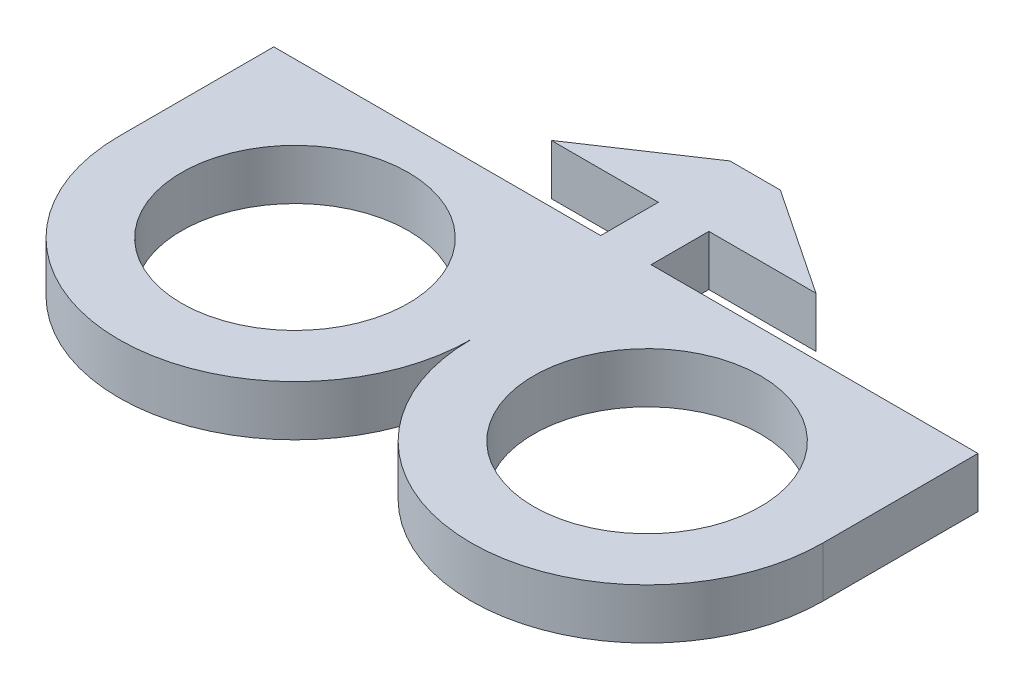
SolidWorks part; units mm, degrees
ref_plane "Front" through (0, 0, 0) normal (0, 0, 1) x (1, 0, 0)
ref_plane "Top" through (0, 0, 0) normal (0, 1, 0) x (1, 0, 0)
ref_plane "Right" through (0, 0, 0) normal (1, 0, 0) x (0, 0, -1)
sketch "Sketch1" plane through (0, 0, 0) normal (0, 1, 0) x (1, 0, 0)
  line L0 (-1.7907, 2.05) -> (-9.398, 2.05)
  line L2 (-1.7907, -2.05) -> (-1.7907, 2.05)
  line L4 (1.7907, -2.05) -> (1.7907, 2.05)
  line L7 (-9.398, 2.05) -> (-1.7907, 7.13)
  line L8 (-1.7907, 7.13) -> (1.7907, 7.13)
  line L9 (1.7907, 7.13) -> (9.398, 2.05)
  line L10 (9.398, 2.05) -> (1.7907, 2.05)
  line L11 (1.7907, -2.05) -> (25.0063, -2.05)
  line L12 (-1.7907, -2.05) -> (-25.0063, -2.05)
  line L13 (-25.0063, -2.05) -> (-25.0063, -13.0482)
  line L14 (-25.0063, -13.0482) -> (25.0063, -13.0482)
  line L15 (25.0063, -13.0482) -> (25.0063, -2.05)
  line L16 (25.0063, -2.05) -> (1.7907, -2.05)
  point P0 (0, 0)
  point P17 (0, 7.13)
  point P19 (0, -13.0482)
  point P24 (1.7907, 0)
  dimension "D1" = 18.796
  dimension "D2" = 3.5814
  dimension "D3" = 50.0126
  dimension "D4" = 10.9982
  dimension "D5" = 5.08
  dimension "D7" = 4.1
extrude "Boss-Extrude1" add sketch "Sketch1" along normal blind 3.5814 contours L14 L15 L11 L4 L10 L9 L8 L7 L0 L2 L12 L13 region at (0, 0, 6.3134)
sketch "Sketch3" plane through (0, 3.5814, 0) normal (0, 1, 0) x (1, 0, 0)
  line L3 (-25.0063, -13.0482) -> (25.0063, -13.0482) construction
  line L16 (-25.0063, -13.0482) -> (25.0063, -13.0482)
  line L17 (25.0063, -13.0482) -> (25.0063, -2.05)
  line L18 (25.0063, -2.05) -> (1.7907, -2.05)
  line L19 (1.7907, -2.05) -> (1.7907, 2.05)
  line L20 (1.7907, 2.05) -> (9.398, 2.05)
  line L21 (9.398, 2.05) -> (1.7907, 7.13)
  line L22 (1.7907, 7.13) -> (-1.7907, 7.13)
  line L23 (-1.7907, 7.13) -> (-9.398, 2.05)
  line L24 (-9.398, 2.05) -> (-1.7907, 2.05)
  line L25 (-1.7907, 2.05) -> (-1.7907, -2.05)
  line L26 (-1.7907, -2.05) -> (-25.0063, -2.05)
  line L27 (-25.0063, -2.05) -> (-25.0063, -13.0482)
  line L28 (-25.0063, -13.0482) -> (25.0063, -13.0482)
  arc A2 (-25.0063, -13.0482) -> (0, -13.0482) centre (-12.5031, -13.0482) ccw
  arc A3 (0, -13.0482) -> (25.0063, -13.0482) centre (12.5032, -13.0482) ccw
  line M15 (-25.0063, -13.0482) -> (25.0063, -13.0482)
  dimension "D1" = 0
extrude "Boss-Extrude2" add sketch "Sketch3" against normal up to surface (3.5814 mm away) contours A2 M15 | L28 A3 region at (-12.5031, 3.5814, 18.3547) region at (12.5032, 3.5814, 18.3547) up to face at (0, 0, 0.9864)
sketch "Sketch4" plane through (0, 3.5814, 0) normal (0, 1, 0) x (1, 0, 0)
  circle A0 centre (-12.5031, -13.0482) radius 8.0518
  circle A1 centre (12.5032, -13.0482) radius 8.0518
  arc A2 (-25.0063, -13.0482) -> (0, -13.0482) centre (-12.5031, -13.0482) ccw construction
  arc A3 (0, -13.0482) -> (25.0063, -13.0482) centre (12.5032, -13.0482) ccw construction
  dimension "D1" = 16.1036
extrude "Cut-Extrude2" cut sketch "Sketch4" against normal through all
